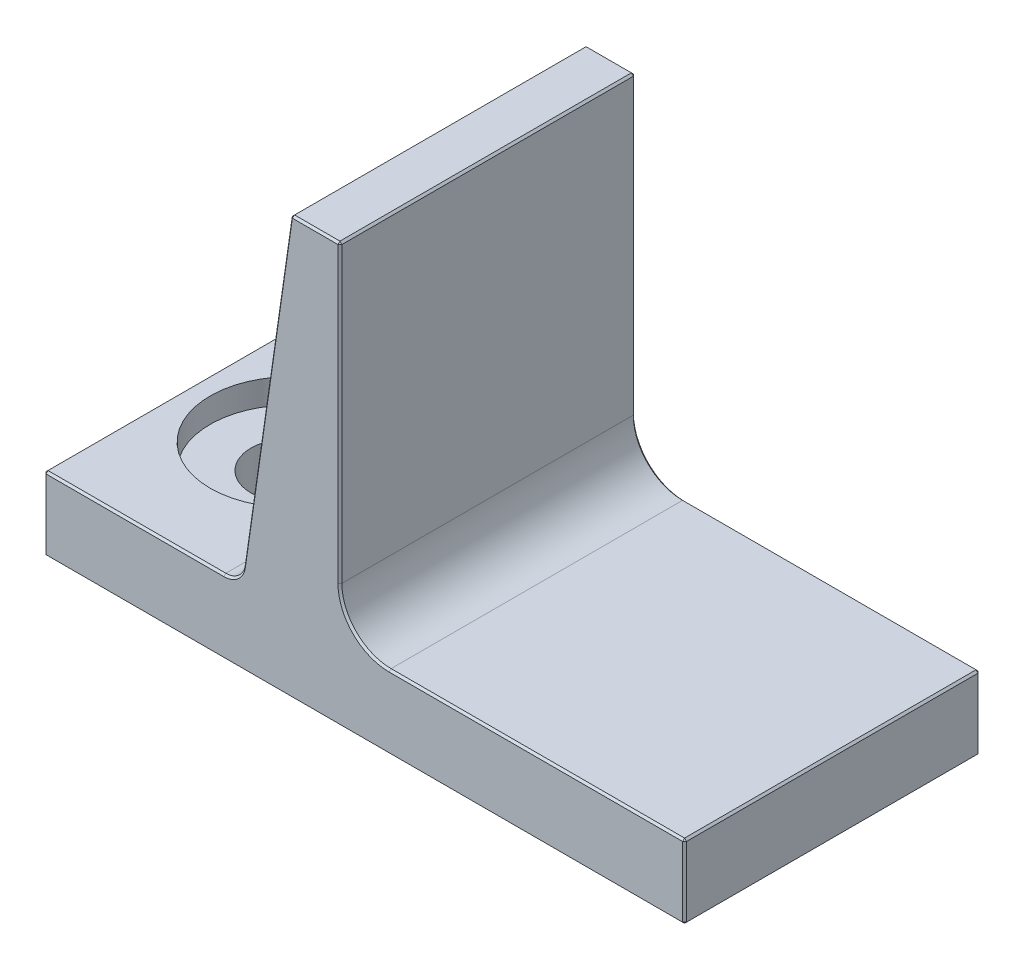
SolidWorks part; units mm, degrees
material "Ti-6Al-2Sn-2Zr-2Mo-2Cr-0.25Si (SS)"
ref_plane "Front Plane" through (0, 0, 0) normal (0, 0, 1) x (1, 0, 0)
ref_plane "Top Plane" through (0, 0, 0) normal (0, 1, 0) x (1, 0, 0)
ref_plane "Right Plane" through (0, 0, 0) normal (1, 0, 0) x (0, 0, -1)
sketch "Sketch1" plane through (0, 0, 0) normal (0, 0, 1) x (1, 0, 0)
  line L0 (0, 0) -> (44.45, 0)
  line L1 (44.45, 0) -> (44.45, -9.525)
  line L2 (44.45, -9.525) -> (-38.1608, -9.525)
  line L3 (-38.1608, -9.525) -> (-38.1608, 0)
  line L4 (-38.1608, 0) -> (-12.7608, 0)
  line L5 (-12.7608, 0) -> (-6.35, 44.45)
  line L6 (-6.35, 44.45) -> (0, 44.45)
  line L7 (0, 44.45) -> (0, 0)
  dimension "D1" = 44.45
  dimension "D2" = 44.45
  dimension "D3" = 9.525
  dimension "D4" = 38.1608
  dimension "D5" = 6.35
  dimension "D6" = 25.4
extrude "Boss-Extrude1" add sketch "Sketch1" along normal blind 38.1
hole_wizard "CBORE for 3/8 Binding Head Machine Screw1" positions "Sketch6" profile "Sketch3" counterbore size "3/8" standard "ANSI Inch" end condition through all
sketch "Sketch6" plane through (0, 0, 0) normal (0, 1, 0) x (1, 0, 0)
  line L0 (-12.7608, 0) -> (-38.1608, 0) construction
  line L1 (-38.1608, -38.1) -> (-38.1608, 0) construction
  point P0 (-25.4608, -19.05)
  point P5 (-25.4608, 0)
  point P8 (-38.1608, -19.05)
sketch "Sketch3" plane through (-25.4608, 0, 19.05) normal (1, 0, 0) x (0, 0, 1)
  line L0 (0, 0) -> (0, 9.525)
  line L1 (0, 9.525) -> (5.0419, 9.525)
  line L3 (5.0419, 9.525) -> (5.0419, 3.175)
  line L4 (10.3187, 3.175) -> (5.0419, 3.175)
  line L5 (10.3187, 3.175) -> (10.3187, 0)
  line L7 (10.3187, 0) -> (0, 0)
  line L11 (0, 0) -> (0, 107.95) construction
  dimension "Thru Hole Dia." = 10.0838
  dimension "Thru Hole Depth" = 9.525
  dimension "C'Bore Depth" = 3.175
fillet "Fillet1" radius 2.54 1 edges at (-12.7608, 0, 19.05)
fillet "Fillet2" radius 6.35 1 edges at (0, 0, 19.05)
chamfer "Chamfer1" distance 0.254 angle 45 26 edges at (-6.35, 44.45, 19.05) (-3.175, 44.45, 0) (-9.3984, 23.3137, 0) (-13.2978, 0.62, 0) (-26.5608, 0, 0) (-38.1608, -4.7625, 0) (3.1446, -9.525, 0) (44.45, -4.7625, 0) (25.4, 0, 0) (1.8599, 1.8599, 0) (0, 25.4, 0) (44.45, -4.7625, 38.1) (44.45, -9.525, 19.05) (3.1446, -9.525, 38.1) (-38.1608, -9.525, 19.05) (-38.1608, -4.7625, 38.1) (-38.1608, 0, 19.05) (-26.5608, 0, 38.1) (-13.2978, 0.62, 38.1) (-9.3984, 23.3137, 38.1) (-3.175, 44.45, 38.1) (0, 44.45, 19.05) (0, 25.4, 38.1) (1.8599, 1.8599, 38.1) (25.4, 0, 38.1) (44.45, 0, 19.05) first distance on face at (-3.175, 44.45, 19.05) first distance on face at (-9.3984, 23.3137, 19.05) first distance on face at (-13.5008, 0.8544, 19.05) first distance on face at (-25.4608, 0, 29.3687) first distance on face at (-38.1608, -4.7625, 19.05) first distance on face at (-25.4608, -9.525, 24.0919) first distance on face at (44.45, -4.7625, 19.05) first distance on face at (-1.5738, 7.6594, 0) first distance on face at (2.5174, 2.5174, 19.05) first distance on face at (0, 25.4, 19.05) first distance on face at (-1.5738, 7.6594, 38.1)
